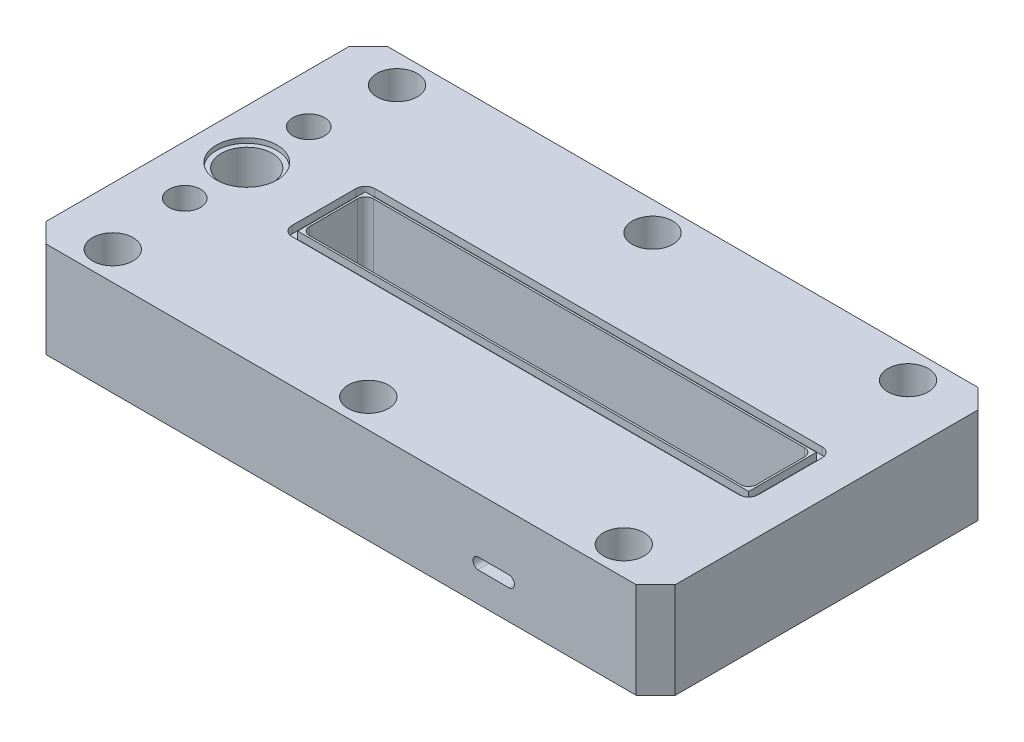
SolidWorks part; units mm, degrees
material "Custom Plastic"
ref_plane "Front Plane" through (0, 0, 0) normal (0, 0, 1) x (1, 0, 0)
ref_plane "Top Plane" through (0, 0, 0) normal (0, 1, 0) x (1, 0, 0)
ref_plane "Right Plane" through (0, 0, 0) normal (1, 0, 0) x (0, 0, -1)
sketch "Sketch1" plane through (0, 0, 0) normal (0, 1, 0) x (1, 0, 0)
  line L1 (0, 0) -> (197, 0)
  line L2 (0, 0) -> (0, 107)
  line L3 (0, 107) -> (197, 107)
  line L4 (197, 0) -> (197, 107)
  dimension "D1" = 197
  dimension "D2" = 107
extrude "Boss-Extrude1" add sketch "Sketch1" along normal blind 30
ref_plane "Left" through (197, 0, 0) normal (1, 0, 0) x (0, 0, -1)
ref_plane "Bot" through (0, 30, 0) normal (0, 1, 0) x (1, 0, 0)
ref_plane "der loco" through (0, 0, -51) normal (0, 0, -1) x (-1, 0, 0)
sketch "Sketch4" plane through (0, 0, 0) normal (0, 1, 0) x (1, 0, 0)
  line L0 (0, 107) -> (0, 0) construction
  line L1 (7.5, 31) -> (189.5, 31)
  line L2 (7.5, 31) -> (7.5, 76)
  line L3 (7.5, 76) -> (189.5, 76)
  line L4 (189.5, 31) -> (189.5, 76)
  line L5 (0, 0) -> (197, 0) construction
  dimension "D1" = 182
  dimension "D2" = 7.5
  dimension "D3" = 45
  dimension "D4" = 31
extrude "Cut-Extrude2" cut sketch "Sketch4" along normal blind 10
ref_plane "Plane32" through (0, 10, 0) normal (0, -1, 0) x (-1, 0, 0)
sketch "Sketch5" plane through (197, 0, 0) normal (1, 0, 0) x (0, 0, -1)
  line L0 (53.5, 30) -> (107, 24.8485)
  line L1 (0, 30) -> (107, 30) construction
  line L2 (107, 24.8485) -> (107, 30)
  line L3 (107, 30) -> (53.5, 30)
  line L4 (107, 30) -> (107, 0) construction
  dimension "D1" = 5.5
  dimension "D2" = 53.5
ref_plane "Plane24" through (0, 10, 0) normal (0, -1, 0) x (-1, 0, 0)
sketch "Sketch53" plane through (0, 10, 0) normal (0, -1, 0) x (-1, 0, 0)
  line L0 (-7.5, 51) -> (-7.5, 31)
  line L1 (-7.5, 76) -> (-7.5, 31) construction
  line L2 (-7.5, 31) -> (-38.5, 31)
  line L3 (-7.5, 31) -> (-189.5, 31) construction
  line L4 (-38.5, 31) -> (-7.5, 51)
  line L5 (-7.5, 53.5) -> (-189.5, 53.5) construction
  line L6 (-189.5, 31) -> (-189.5, 76) construction
  line L7 (-7.5, 56) -> (-7.5, 76)
  line L8 (-7.5, 76) -> (-38.5, 76)
  line L9 (-38.5, 76) -> (-7.5, 56)
  dimension "D1" = 31
  dimension "D2" = 20
extrude "Boss-Extrude11" add sketch "Sketch53" along normal up to surface (10 mm away) up to face at (98.5, 0, -53.5)
ref_plane "izq loco" through (0, 0, -56) normal (0, 0, -1) x (-1, 0, 0)
sketch "Sketch18" plane through (197, 0, 0) normal (1, 0, 0) x (0, 0, -1)
  line L0 (0, 23.431) -> (0, 30)
  line L1 (0, 30) -> (0, 0) construction
  line L2 (0, 30) -> (53.5, 30)
  line L3 (53.5, 30) -> (0, 23.431)
  line L4 (0, 30) -> (107, 30) construction
  dimension "D1" = 53.5
  dimension "D2" = 7
sketch "Sketch60" plane through (0, 0, 0) normal (0, 1, 0) x (1, 0, 0)
  point P0 (7.5, 31)
  point P1 (38.5, 31)
  point P2 (7.5, 76)
  point P6 (38.5, 76)
  dimension "D1" = 20
  dimension "D2" = 31
  dimension "D3" = 20
  dimension "D4" = 31
ref_axis "Axis6" through (7.5, 0, -31) along (1, 0, 0)
sketch "Sketch69" plane through (0, 10, 0) normal (0, -1, 0) x (-1, 0, 0)
  point P0 (-38.5, 56)
  point P1 (-7.5, 51)
  point P2 (-37.5, 51)
  point P3 (-7.5, 56)
  dimension "D1" = 31
  dimension "D2" = 20
  dimension "D3" = 20
  dimension "D4" = 30
sketch "der loco axis" plane through (0, 0, -51) normal (0, 0, -1) x (-1, 0, 0)
  point P0 (-7.5, 8.5)
  point P1 (-37.5, 8.5)
  dimension "D1" = 1.5
sketch "izq loco axis" plane through (0, 0, -56) normal (0, 0, -1) x (-1, 0, 0)
  line L0 (-38.5, 0) -> (-38.5, 10) construction
  line L1 (-7.5, 0) -> (-7.5, 10) construction
  point P0 (-7.5, 8.5)
  point P1 (-38.5, 8.5)
  dimension "D1" = 1.5
ref_axis "Axis8" through (38.5, 0, -76) along (-1, 0, 0)
ref_axis "Axis9" through (7.5, 8.5, -56) along (1, 0, 0)
ref_axis "Axis10" through (37.5, 8.5, -51) along (-1, 0, 0)
ref_plane "Izq bueno" through (0, 27.3584, -11.6273) normal (0, 0.9203, -0.3911) x (1, 0, 0)
sketch "Izq" plane through (0, 27.3584, -11.6273) normal (0, 0.9203, -0.3911) x (1, 0, 0)
  line L0 (7.5, 48.2138) -> (38.5, 69.9451)
  line L1 (38.5, 69.9451) -> (7.5, 69.9451)
  line L2 (7.5, 69.9451) -> (7.5, 48.2138)
extrude "Cut-Extrude28" cut sketch "Izq" against normal blind 14.5
ref_plane "Der bueno" through (0, -11.1593, -4.7427) normal (0, 0.9203, 0.3911) x (1, 0, 0)
sketch "Der" plane through (0, -11.1593, -4.7427) normal (0, 0.9203, 0.3911) x (1, 0, 0)
  line L0 (7.5, 50.2616) -> (38.5, 28.5303)
  line L1 (38.5, 28.5303) -> (7.5, 28.5303)
  line L2 (7.5, 28.5303) -> (7.5, 50.2616)
sketch "Sketch9" plane through (0, 30, 0) normal (0, 1, 0) x (1, 0, 0)
  line L0 (0, 107) -> (0, 0) construction
  circle A0 centre (15.45, 53.5) radius 8
  point P6 (0, 53.5)
  dimension "D1" = 16
  dimension "D2" = 15.45
extrude "Cut-Extrude6" cut sketch "Sketch9" against normal blind 171
sketch "Sketch10" plane through (0, 30, 0) normal (0, 1, 0) x (1, 0, 0)
  circle A0 centre (15.45, 53.5) radius 9.5
  dimension "D1" = 19
extrude "Cut-Extrude7" cut sketch "Sketch10" against normal blind 1.5
sketch "Sketch11" plane through (0, 30, 0) normal (0, 1, 0) x (1, 0, 0)
  line L1 (15.45, 61.5) -> (15.45, 53.5) construction
  line L3 (197, 107) -> (0, 107) construction
  line L4 (0, 0) -> (197, 0) construction
  circle A0 centre (15.45, 72.9051) radius 4.95
  circle A1 centre (15.45, 34.0949) radius 4.95
  circle A6 centre (15.45, 53.5) radius 8 construction
  dimension "D1" = 9.9
  dimension "D3" = 9.9
  dimension "D2" = 34.0949
  dimension "D4" = 34.0949
extrude "Cut-Extrude8" cut sketch "Sketch11" against normal blind 17.6
sketch "Sketch41" plane through (0, 0, 0) normal (0, 1, 0) x (1, 0, 0)
  line L0 (197, 0) -> (197, 107) construction
  line L1 (197, 107) -> (0, 107) construction
  line L2 (0, 0) -> (197, 0) construction
  circle A0 centre (138.5, 9) radius 2.9
  circle A1 centre (138.5, 98) radius 2.9
  dimension "D1" = 5.8
  dimension "D4" = 5.8
  dimension "D2" = 58.5
  dimension "D3" = 58.5
  dimension "D5" = 9
  dimension "D6" = 9
extrude "Cut-Extrude21" cut sketch "Sketch41" along normal blind 7
sketch "Sketch42" plane through (0, 0, 0) normal (0, 0, 1) x (1, 0, 0)
  line L0 (197, 30) -> (197, 0) construction
  line L5 (0, 0) -> (197, 0) construction
  line L6 (141.2615, 12.7727) -> (151, 12.7727)
  line L7 (141.2615, 9.2727) -> (151, 9.2273)
  arc A0 (141.2615, 12.7727) -> (141.2615, 9.2727) centre (141.5457, 11.0227) ccw
  arc A2 (151, 12.7727) -> (151, 9.2273) centre (151, 11) cw
  dimension "D4" = 0.268
  dimension "D2" = 1.7727
  dimension "D3" = 1.7729
  dimension "D1" = 9.7385
  dimension "D5" = 46
  dimension "D6" = 11
extrude "Cut-Extrude22" cut sketch "Sketch42" against normal blind 10
ref_plane "Plane19" through (0, 0, -107) normal (0, 0, -1) x (-1, 0, 0)
sketch "Sketch43" plane through (0, 0, -107) normal (0, 0, -1) x (-1, 0, 0)
  line L0 (-55.7, 11) -> (-46, 11) construction
  line L1 (-55.7, 12.8) -> (-46, 12.8)
  line L2 (-55.7, 9.2) -> (-46, 9.2)
  line L3 (-197, 0) -> (0, 0) construction
  line L4 (0, 30) -> (0, 0) construction
  arc A0 (-55.7, 12.8) -> (-55.7, 9.2) centre (-55.7, 11) ccw
  arc A1 (-46, 9.2) -> (-46, 12.8) centre (-46, 11) ccw
  point P2 (-50.85, 11)
  dimension "D2" = 1.8
  dimension "D1" = 9.7
  dimension "D3" = 11
  dimension "D4" = 46
extrude "Cut-Extrude23" cut sketch "Sketch43" against normal blind 10
extrude "Cut-Extrude29" cut sketch "Der" against normal blind 14.5
sketch "Sketch85" plane through (0, 30, 0) normal (0, 1, 0) x (1, 0, 0)
  line L0 (0, 100.9) -> (6.1, 107)
  line L3 (6.1, 107) -> (0, 107)
  line L4 (0, 107) -> (0, 100.9)
  line L5 (0, 0) -> (6.1, 0)
  line L7 (6.1, 0) -> (0, 6.1)
  line L9 (0, 6.1) -> (0, 0)
  line L10 (197, 6.1) -> (190.9, 0)
  line L13 (190.9, 0) -> (197, 0)
  line L14 (197, 0) -> (197, 6.1)
  line L15 (197, 107) -> (190.9, 107)
  line L17 (190.9, 107) -> (197, 100.9)
  line L19 (197, 100.9) -> (197, 107)
  point P2 (0, 0)
  point P3 (0, 0)
  point P4 (0, 0)
  point P5 (0, 0)
  point P11 (0, 0)
  dimension "D1" = 6.1
  dimension "D2" = 6.1
  dimension "D3" = 6.1
  dimension "D4" = 6.1
  dimension "D5" = 6.1
  dimension "D6" = 6.1
  dimension "D7" = 6.1
  dimension "D8" = 8.6267
  dimension "D9" = 8.6267
extrude "Cut-Extrude36" cut sketch "Sketch85" against normal blind 55.4
sketch "Sketch90" plane through (0, 30, 0) normal (0, 1, 0) x (1, 0, 0)
  line L0 (190.9, 107) -> (6.1, 107) construction
  line L1 (0, 100.9) -> (0, 6.1) construction
  line L3 (6.1, 0) -> (190.9, 0) construction
  circle A0 centre (18, 9) radius 6.35
  circle A1 centre (98, 9) radius 6.35
  circle A2 centre (178, 9) radius 6.35
  circle A3 centre (98, 98) radius 6.35
  circle A4 centre (178, 98) radius 6.35
  circle A5 centre (18, 98) radius 6.35
  dimension "D1" = 12.7
  dimension "D5" = 98
  dimension "D6" = 80
  dimension "D7" = 9
  dimension "D8" = 18
  dimension "D4" = 9
  dimension "D2" = 3
  dimension "D3" = 2
extrude "Cut-Extrude38" cut sketch "Sketch90" against normal blind 17
ref_plane "Plane33" through (38.5, 0, 0) normal (1, 0, 0) x (0, 0, -1)
sketch "Sketch91" plane through (0, 30, 0) normal (0, 1, 0) x (1, 0, 0)
  line L0 (42.6, 66.5) -> (182.6, 66.5)
  line L1 (39.6, 63.5) -> (39.6, 43.5)
  line L2 (42.6, 40.5) -> (182.6, 40.5)
  line L3 (185.6, 63.5) -> (185.6, 43.5)
  line L4 (42, 42.9) -> (183.2, 42.9)
  line L5 (42, 42.9) -> (42, 64.1)
  line L6 (42, 64.1) -> (183.2, 64.1)
  line L7 (183.2, 42.9) -> (183.2, 64.1)
  line L9 (190.9, 107) -> (6.1, 107) construction
  line L10 (197, 6.1) -> (197, 100.9) construction
  arc A0 (182.6, 66.5) -> (185.6, 63.5) centre (182.6, 63.5) cw
  arc A1 (182.6, 40.5) -> (185.6, 43.5) centre (182.6, 43.5) ccw
  arc A2 (39.6, 43.5) -> (42.6, 40.5) centre (42.6, 43.5) ccw
  arc A3 (42.6, 66.5) -> (39.6, 63.5) centre (42.6, 63.5) ccw
  point P12 (185.6, 53.5)
  point P17 (112.6, 66.5)
  point P24 (98.5, 107)
  dimension "D1" = 3
  dimension "D2" = 20
  dimension "D3" = 146
  dimension "D4" = 2.4
  dimension "D5" = 2.4
  dimension "D6" = 2.4
  dimension "D7" = 2.4
  dimension "D8" = 11.4
extrude "Cut-Extrude39" cut sketch "Sketch91" against normal blind 2.3
sketch "Sketch93" plane through (0, 30, 0) normal (0, 1, 0) x (1, 0, 0)
  line L0 (42, 42.9) -> (183.2, 42.9) construction
  line L1 (45.1, 43.5) -> (180.1, 43.5)
  line L2 (42.6, 46) -> (42.6, 61)
  line L3 (45.1, 63.5) -> (180.1, 63.5)
  line L4 (182.6, 46) -> (182.6, 61)
  line L5 (42, 64.1) -> (42, 42.9) construction
  arc A0 (45.1, 43.5) -> (42.6, 46) centre (45.1, 46) cw
  arc A1 (42.6, 61) -> (45.1, 63.5) centre (45.1, 61) cw
  arc A2 (180.1, 63.5) -> (182.6, 61) centre (180.1, 61) cw
  arc A3 (180.1, 43.5) -> (182.6, 46) centre (180.1, 46) ccw
  point P4 (112.6, 43.5)
  point P7 (112.6, 42.9)
  point P8 (42.6, 53.5)
  point P11 (42, 53.5)
  point P14 (42.6, 43.5)
  point P17 (42.6, 63.5)
  point P20 (182.6, 63.5)
  dimension "D3" = 2.5
  dimension "D1" = 20
  dimension "D2" = 140
extrude "Cut-Extrude40" cut sketch "Sketch93" against normal through all
sketch "Sketch94" plane through (197, 0, 0) normal (1, 0, 0) x (0, 0, -1)
  line L0 (53.5, 0) -> (53.5, 100) construction
  line L1 (6.1, 0) -> (100.9, 0) construction
  dimension "D1" = 100
